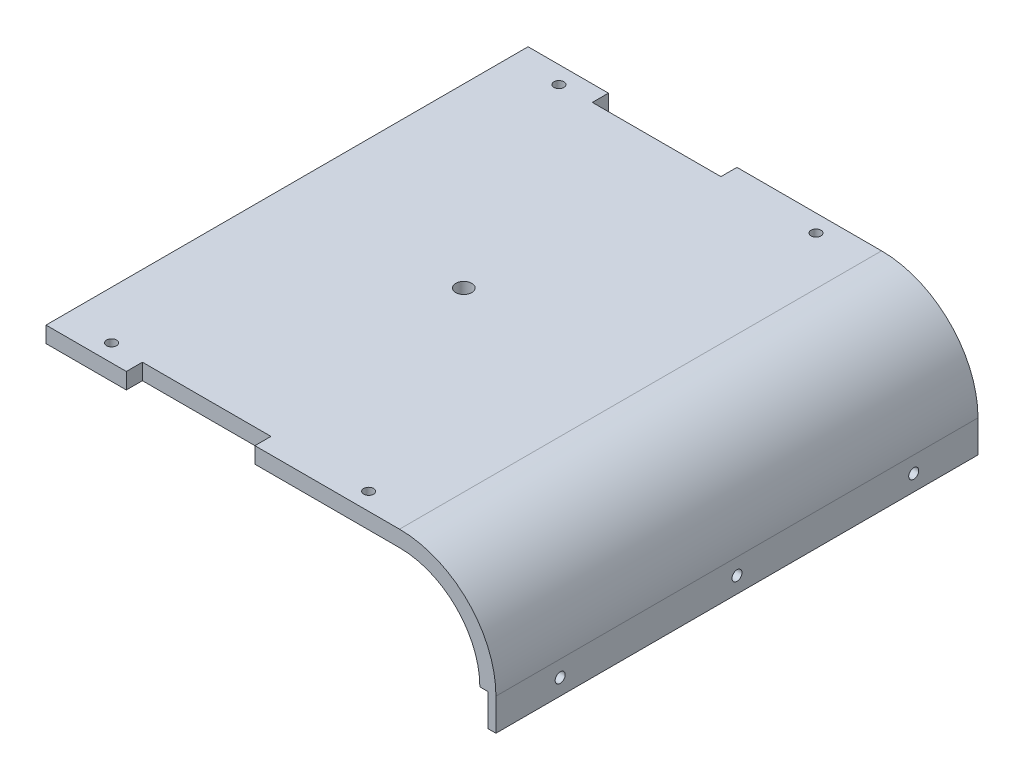
SolidWorks part; units mm, degrees
ref_plane "Front Plane" through (0, 0, 0) normal (0, 0, 1) x (1, 0, 0)
ref_plane "Top Plane" through (0, 0, 0) normal (0, 1, 0) x (1, 0, 0)
ref_plane "Right Plane" through (0, 0, 0) normal (1, 0, 0) x (0, 0, -1)
sketch "Sketch1" plane through (0, 0, 0) normal (0, 0, 1) x (1, 0, 0)
  line L0 (-139.7, 0) -> (139.7, 0)
  line L1 (139.7, 0) -> (139.7, -152.4) construction
  line L2 (139.7, -76.2) -> (215.9, -76.2) construction
  line L3 (-139.7, -12.7) -> (139.7, -12.7)
  line L4 (-139.7, 0) -> (-139.7, -12.7)
  line L5 (215.9, -76.2) -> (203.2, -76.2)
  circle A0 centre (139.7, -76.2) radius 76.2 construction
  arc A1 (139.7, 0) -> (215.9, -76.2) centre (139.7, -76.2) cw
  arc A2 (139.7, -12.7) -> (203.2, -76.2) centre (139.7, -76.2) cw
  point P4 (0, 0)
  dimension "D1" = 152.4
  dimension "D2" = 355.6
  dimension "D3" = 12.7
extrude "Boss-Extrude1" add sketch "Sketch1" along normal blind 190.5 and the other way blind 190.5
sketch "Sketch2" plane through (0, -76.2, 0) normal (0, -1, 0) x (1, 0, 0)
  line L0 (203.2, 190.5) -> (215.9, 190.5) construction
  line L1 (209.55, 190.5) -> (215.9, 190.5)
  line L2 (209.55, 190.5) -> (209.55, -190.5)
  line L3 (209.55, -190.5) -> (215.9, -190.5)
  line L4 (215.9, 190.5) -> (215.9, -190.5)
extrude "Boss-Extrude2" add sketch "Sketch2" along normal blind 25.4
sketch "Sketch3" plane through (215.9, 0, 0) normal (1, 0, 0) x (0, 0, -1)
  line L0 (-190.5, -88.9) -> (190.5, -88.9) construction
  line L1 (-190.5, -101.6) -> (-190.5, -76.2) construction
  line L2 (190.5, -101.6) -> (190.5, -76.2) construction
  line L3 (0, -76.2) -> (0, -101.6) construction
  line L4 (190.5, -76.2) -> (-190.5, -76.2) construction
  line L5 (190.5, -101.6) -> (-190.5, -101.6) construction
  line L6 (139.7, -76.2) -> (139.7, -101.6) construction
  line L7 (-139.7, -76.2) -> (-139.7, -101.6) construction
  circle A0 centre (-139.7, -88.9) radius 3.9687
  circle A1 centre (0, -88.9) radius 3.9687
  circle A2 centre (139.7, -88.9) radius 3.9687
  dimension "D3" = 7.9375
  dimension "D1" = 139.7
  dimension "D2" = 139.7
extrude "Cut-Extrude1" cut sketch "Sketch3" against normal blind 25.4
sketch "Sketch4" plane through (0, 0, 0) normal (0, 1, 0) x (1, 0, 0)
  circle A0 centre (0, 0) radius 6.35
  dimension "D1" = 12.7
extrude "Cut-Extrude2" cut sketch "Sketch4" against normal blind 17.78
sketch "Sketch5" plane through (0, 0, 0) normal (0, 1, 0) x (1, 0, 0)
  line L0 (139.7, 0) -> (101.6, 0) construction
  line L1 (139.7, 190.5) -> (139.7, -190.5) construction
  line L2 (-139.7, 190.5) -> (-139.7, -190.5) construction
  line L3 (0, 176.784) -> (0, -176.784) construction
  line L4 (101.6, 176.784) -> (101.6, -176.784) construction
  line L5 (-101.6, -176.784) -> (-101.6, 176.784) construction
  line L6 (139.7, -190.5) -> (-139.7, -190.5) construction
  line L7 (-101.6, 0) -> (-139.7, 0) construction
  line L8 (-101.6, 0) -> (0, 0) construction
  line L9 (0, 0) -> (101.6, 0) construction
  line L10 (0, -190.5) -> (-76.2, -190.5)
  line L11 (-76.2, -190.5) -> (-76.2, -177.8)
  line L12 (-101.6, 0) -> (0, -176.784) construction
  line L13 (0, 0) -> (-101.6, -176.784) construction
  line L14 (-50.8, -88.392) -> (-50.8, -190.5) construction
  line L15 (-50.8, -190.5) -> (-101.6, -176.784) construction
  line L16 (-76.2, -183.642) -> (-76.2, -132.588) construction
  line L17 (-76.2, -177.8) -> (0, -177.8)
  line L18 (0, -177.8) -> (25.4, -177.8)
  line L19 (25.4, -177.8) -> (25.4, -190.5)
  line L20 (25.4, -190.5) -> (0, -190.5)
  line L21 (25.4, 177.8) -> (25.4, 190.5)
  line L22 (0, 177.8) -> (25.4, 177.8)
  line L23 (-76.2, 177.8) -> (0, 177.8)
  line L24 (-76.2, 190.5) -> (-76.2, 177.8)
  line L25 (0, 190.5) -> (-76.2, 190.5)
  line L26 (25.4, 190.5) -> (0, 190.5)
  circle A0 centre (-101.6, -176.784) radius 3.937
  circle A1 centre (101.6, -176.784) radius 3.937
  circle A2 centre (101.6, 176.784) radius 3.937
  circle A3 centre (-101.6, 176.784) radius 3.937
  point P11 (0, 0)
  point P15 (101.6, 0)
  point P18 (-101.6, 0)
  dimension "D3" = 7.874
  dimension "D1" = 13.716
  dimension "D2" = 203.2
  dimension "D4" = 101.6
  dimension "D5" = 12.7
extrude "Cut-Extrude3" cut sketch "Sketch5" against normal through all
